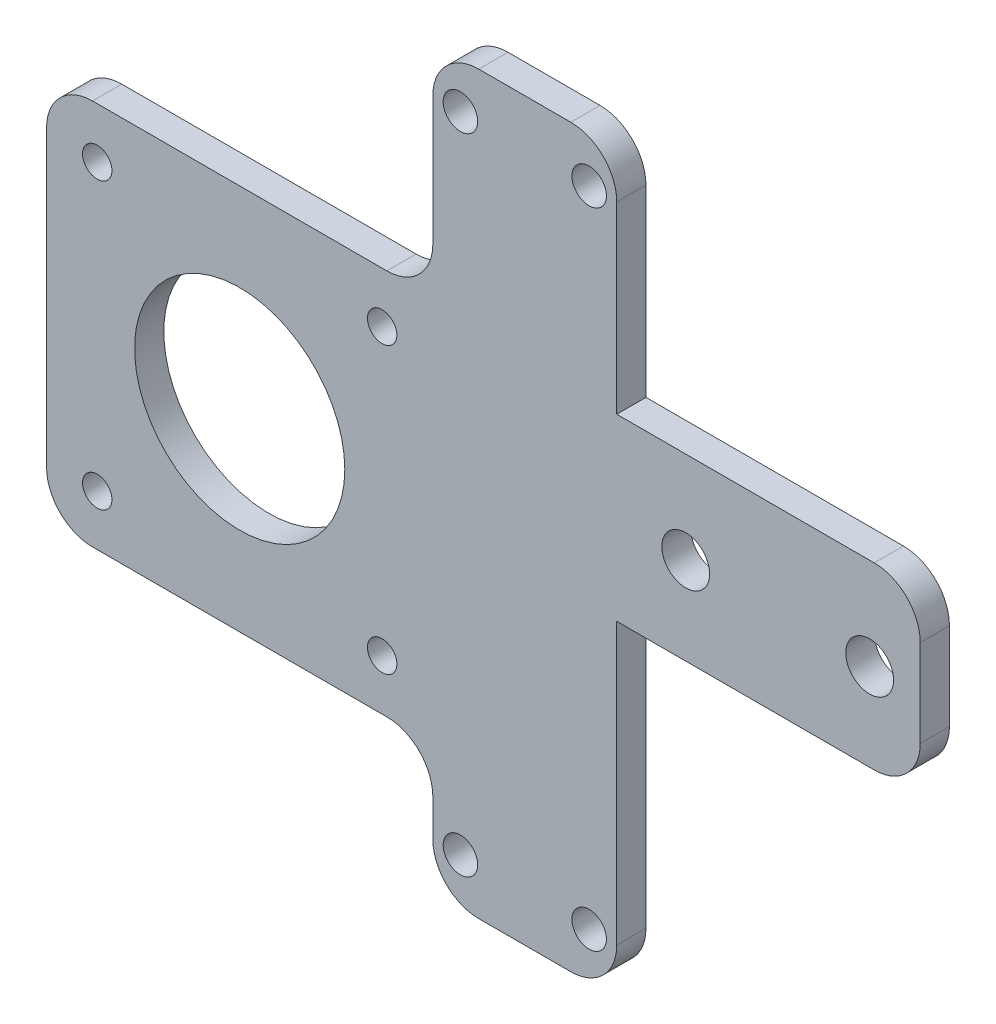
SolidWorks part; units mm, degrees
ref_plane "Front Plane" through (0, 0, 0) normal (0, 0, 1) x (1, 0, 0)
ref_plane "Top Plane" through (0, 0, 0) normal (0, 1, 0) x (1, 0, 0)
ref_plane "Right Plane" through (0, 0, 0) normal (1, 0, 0) x (0, 0, -1)
ref_plane "Plane1" through (0, 0, 3.175) normal (0, 0, 1) x (1, 0, 0)
sketch "Sketch11" plane through (0, 0, 3.175) normal (0, 0, 1) x (1, 0, 0)
  line L0 (-42, 51) -> (-42, 19)
  line L1 (-37, 14) -> (-5, 14)
  line L2 (0, 9) -> (0, 5)
  line L3 (5, 0) -> (15, 0)
  line L4 (20, 5) -> (20, 35.5)
  line L5 (20, 35.5) -> (48, 35.5)
  line L6 (53, 40.5) -> (53, 50)
  line L7 (48, 55) -> (20, 55)
  line L8 (20, 55) -> (20, 75)
  line L9 (15, 80) -> (5, 80)
  line L10 (0, 75) -> (0, 61)
  line L11 (-5, 56) -> (-37, 56)
  arc A0 (-37, 56) -> (-42, 51) centre (-37, 51) ccw
  arc A1 (-42, 19) -> (-37, 14) centre (-37, 19) ccw
  arc A2 (-5, 14) -> (0, 9) centre (-5, 9) cw
  arc A3 (0, 5) -> (5, 0) centre (5, 5) ccw
  arc A4 (15, 0) -> (20, 5) centre (15, 5) ccw
  arc A5 (48, 35.5) -> (53, 40.5) centre (48, 40.5) ccw
  arc A6 (53, 50) -> (48, 55) centre (48, 50) ccw
  arc A7 (20, 75) -> (15, 80) centre (15, 75) ccw
  arc A8 (5, 80) -> (0, 75) centre (5, 75) ccw
  arc A9 (0, 61) -> (-5, 56) centre (-5, 61) cw
base flange "Base-Flange1" sketch "Sketch11" thickness 3.175 reverse thickness direction yes parameters "D1"=0
hole_wizard "M3.5 Clearance Hole1" positions "Sketch17" profile "Sketch16" hole size "M3.5" standard "ANSI Metric"
sketch "Sketch17" plane through (0, 0, 3.175) normal (0, 0, 1) x (1, 0, 0)
  point P0 (17, 75)
  point P1 (3, 5)
  point P2 (3, 75)
  point P3 (17, 5)
sketch "Sketch16" plane through (17, 75, 3.175) normal (1, 0, 0) x (0, -1, 0)
  line L0 (0, 0) -> (0, 3.175)
  line L1 (0, 3.175) -> (1.875, 3.175)
  line L2 (1.875, 3.175) -> (1.875, 0)
  line L5 (1.875, 0) -> (0, 0)
  line L11 (0, -6.35) -> (0, 107.95) construction
  dimension "Thru Hole Dia." = 3.75
  dimension "Thru Hole Depth" = 3.175
hole_wizard "Ø5.2 (5.2) Diameter Hole1" positions "Sketch19" profile "Sketch18" hole size "Ø5.2" standard "ANSI Metric"
sketch "Sketch19" plane through (0, 0, 3.175) normal (0, 0, 1) x (1, 0, 0)
  point P0 (47.5, 45)
  point P1 (27.5, 45)
sketch "Sketch18" plane through (47.5, 45, 3.175) normal (1, 0, 0) x (0, -1, 0)
  line L0 (0, 0) -> (0, 3.175)
  line L1 (0, 3.175) -> (2.6, 3.175)
  line L2 (2.6, 3.175) -> (2.6, 0)
  line L5 (2.6, 0) -> (0, 0)
  line L11 (0, -6.35) -> (0, 107.95) construction
  dimension "Thru Hole Dia." = 5.2
  dimension "Thru Hole Depth" = 3.175
hole_wizard "Ø3.2 (3.2) Diameter Hole1" positions "Sketch21" profile "Sketch20" hole size "Ø3.2" standard "ANSI Metric"
sketch "Sketch21" plane through (0, 0, 3.175) normal (0, 0, 1) x (1, 0, 0)
  point P0 (-36.4909, 50.4909)
  point P1 (-5.5091, 50.4909)
  point P2 (-5.5091, 19.5091)
  point P3 (-36.4909, 19.5091)
sketch "Sketch20" plane through (-36.4909, 50.4909, 3.175) normal (1, 0, 0) x (0, -1, 0)
  line L0 (0, 0) -> (0, 3.175)
  line L1 (0, 3.175) -> (1.6, 3.175)
  line L2 (1.6, 3.175) -> (1.6, 0)
  line L5 (1.6, 0) -> (0, 0)
  line L11 (0, -6.35) -> (0, 107.95) construction
  dimension "Thru Hole Dia." = 3.2
  dimension "Thru Hole Depth" = 3.175
hole_wizard "M20 Clearance Hole1" positions "Sketch23" profile "Sketch22" hole size "M20" standard "ANSI Metric"
sketch "Sketch23" plane through (0, 0, 3.175) normal (0, 0, 1) x (1, 0, 0)
  point P0 (-21, 35)
sketch "Sketch22" plane through (-21, 35, 3.175) normal (1, 0, 0) x (0, -1, 0)
  line L0 (0, 0) -> (0, 3.175)
  line L1 (0, 3.175) -> (11.43, 3.175)
  line L2 (11.43, 3.175) -> (11.43, 0)
  line L5 (11.43, 0) -> (0, 0)
  line L11 (0, -6.35) -> (0, 107.95) construction
  dimension "Thru Hole Dia." = 22.86
  dimension "Thru Hole Depth" = 3.175
ref_point "Point1"
ref_point "Point2"
ref_plane "Plane2" through (0, 45, 0) normal (0, -1, 0) x (-1, 0, 0)
sketch "Bend-Lines4" plane through (0, 0, 0) normal (0, 1, 0) x (1, 0, 0)
sketch "Bounding-Box4" plane through (0, 0, 0) normal (0, 1, 0) x (1, 0, 0)
sheet metal parameters "Sheet-Metal(5)" thickness 3.175 parameters "D1"=0
flat pattern "Flat-Pattern(5)" [suppressed]
sketch "Bend-Lines5" plane through (0, 0, 0) normal (0, 1, 0) x (1, 0, 0)
sketch "Bounding-Box5" [suppressed] plane through (0, 0, 0) normal (0, 1, 0) x (1, 0, 0)
sheet metal parameters "Sheet-Metal(6)" thickness 3.175 parameters "D1"=0
flat pattern "Flat-Pattern(5)"
sketch "Bend-Lines5" plane through (0, 0, 0) normal (0, 1, 0) x (1, 0, 0)
sketch "Bounding-Box5" [suppressed] plane through (0, 0, 0) normal (0, 1, 0) x (1, 0, 0)
sheet metal parameters "Sheet-Metal(7)" thickness 3.175 parameters "D1"=0
flat pattern "Flat-Pattern(5)"
sketch "Bend-Lines5" plane through (0, 0, 0) normal (0, 1, 0) x (1, 0, 0)
sketch "Bounding-Box5" [suppressed] plane through (0, 0, 0) normal (0, 1, 0) x (1, 0, 0)
sheet metal parameters "Sheet-Metal(8)" thickness 3.175 parameters "D1"=0
flat pattern "Flat-Pattern(5)"
sketch "Bend-Lines5" plane through (0, 0, 0) normal (0, 1, 0) x (1, 0, 0)
sketch "Bounding-Box5" [suppressed] plane through (0, 0, 0) normal (0, 1, 0) x (1, 0, 0)
sheet metal parameters "Sheet-Metal(9)" thickness 3.175 parameters "D1"=0
flat pattern "Flat-Pattern(5)"
sketch "Bend-Lines5" plane through (0, 0, 0) normal (0, 1, 0) x (1, 0, 0)
sketch "Bounding-Box5" [suppressed] plane through (0, 0, 0) normal (0, 1, 0) x (1, 0, 0)
